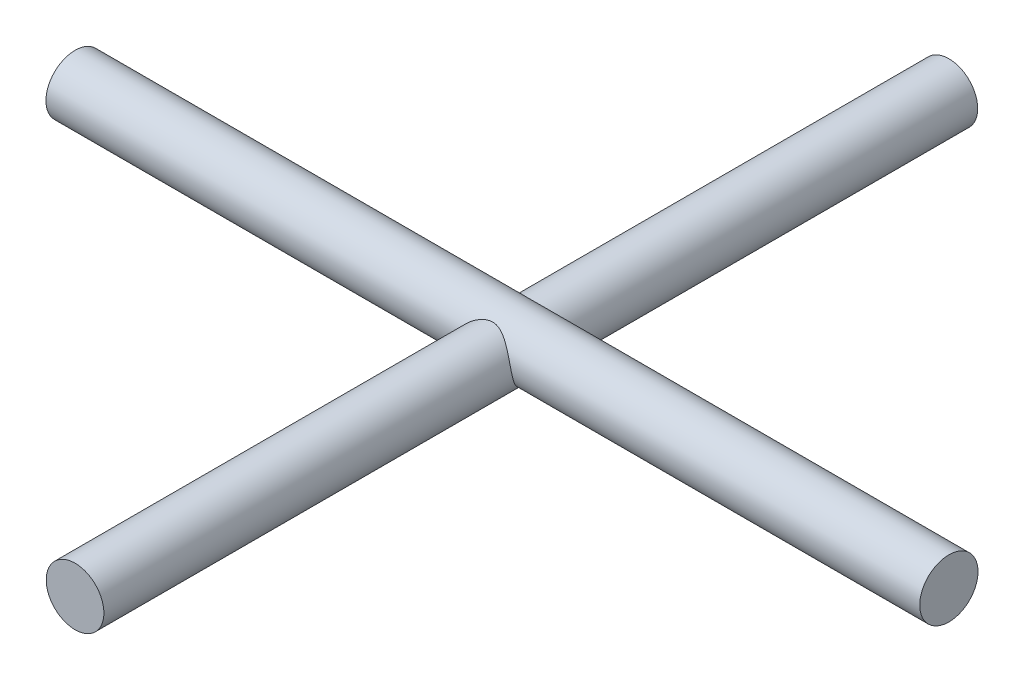
SolidWorks part; units mm, degrees
ref_plane "Front Plane" through (0, 0, 0) normal (0, 0, 1) x (1, 0, 0)
ref_plane "Top Plane" through (0, 0, 0) normal (0, 1, 0) x (1, 0, 0)
ref_plane "Right Plane" through (0, 0, 0) normal (1, 0, 0) x (0, 0, -1)
sketch "Sketch2" plane through (0, 0, 0) normal (0, 0, 1) x (1, 0, 0)
  circle A0 centre (0, 0) radius 2.475
  dimension "D1" = 4.95
extrude "Boss-Extrude1" add sketch "Sketch2" along normal blind 37.5 and the other way blind 37.5
sketch "Sketch3" plane through (0, 0, 0) normal (1, 0, 0) x (0, 0, -1)
  circle A0 centre (0, 0.6) radius 2.5
  dimension "D1" = 5
  dimension "D2" = 0.6
extrude "Boss-Extrude2" add sketch "Sketch3" along normal blind 37.5 and the other way blind 37.5
